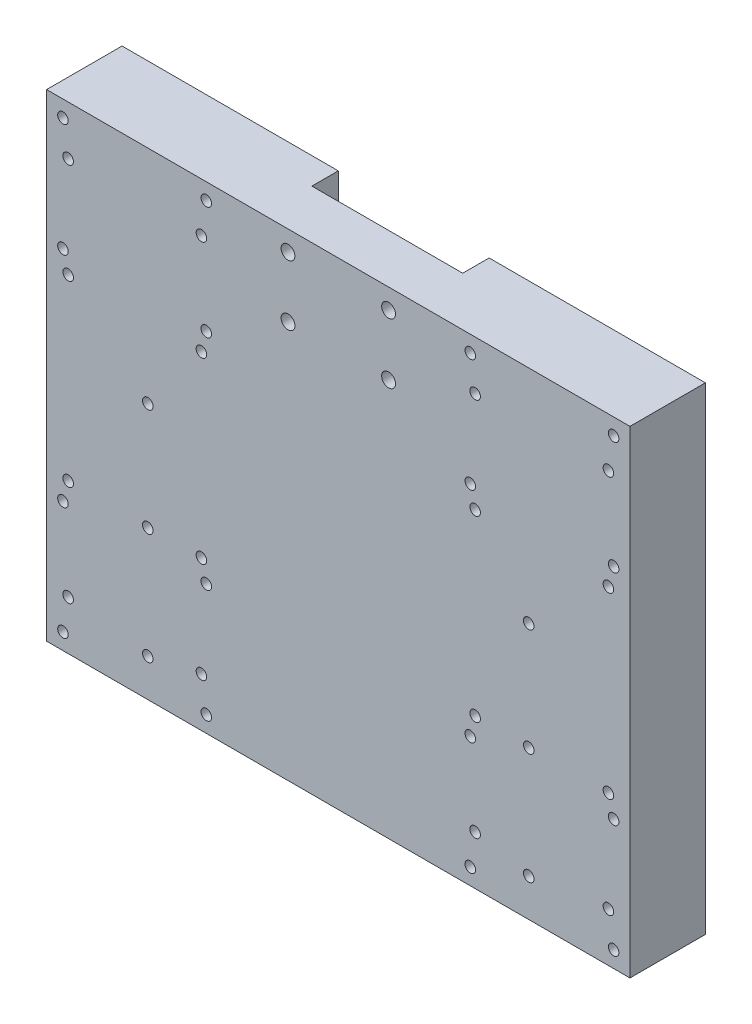
SolidWorks part; units mm, degrees
ref_plane "Piano frontale" through (0, 0, 0) normal (0, 0, 1) x (1, 0, 0)
ref_plane "Piano superiore" through (0, 0, 0) normal (0, 1, 0) x (1, 0, 0)
ref_plane "Piano destro" through (0, 0, 0) normal (1, 0, 0) x (0, 0, -1)
sketch "Schizzo1" plane through (0, 0, 0) normal (0, 0, 1) x (1, 0, 0)
  line L1 (116, -95) -> (-116, -95)
  line L2 (116, -95) -> (116, 95)
  line L3 (116, 95) -> (-116, 95)
  line L4 (-116, -95) -> (-116, 95)
  line L5 (116, -95) -> (-116, 95) construction
  line L6 (116, 95) -> (-116, -95) construction
  point P0 (0, 0)
  dimension "D1" = 232
  dimension "D2" = 190
extrude "Estrusione-Estrusione1" add sketch "Schizzo1" along normal blind 30
sketch "Schizzo3" plane through (0, 0, 30) normal (0, 0, 1) x (1, 0, 0)
  line L0 (20, 7) -> (-20, 7) construction
  line L1 (-20, 7) -> (20, -17) construction
  line L2 (20, -17) -> (20, 7) construction
  line L3 (20, 7) -> (-20, -17) construction
  line L4 (-20, -17) -> (-20, 7) construction
  line L5 (-20, -17) -> (20, -17) construction
  circle A8 centre (20, 7) radius 3
  circle A9 centre (-20, 7) radius 3
  circle A10 centre (-20, -17) radius 3
  circle A11 centre (20, -17) radius 3
  point P21 (0, -5)
  dimension "D1" = 40
  dimension "D2" = 24
sketch "Schizzo4" plane through (0, 95, 0) normal (0, 1, 0) x (1, 0, 0)
  line L0 (116, 0) -> (-116, 0) construction
  line L1 (30, 0) -> (-30, 0)
  line L2 (30, 0) -> (30, -10.5)
  line L3 (30, -10.5) -> (-30, -10.5)
  line L4 (-30, 0) -> (-30, -10.5)
  dimension "D1" = 10.5
extrude "Taglio-Estrusione2" cut sketch "Schizzo4" against normal through all
sketch "Sketch1" plane through (0, 0, 0) normal (0, 0, -1) x (-1, 0, 0)
  line L0 (-52.5, 88.5) -> (-109.5, 88.5) construction
  line L1 (-81, 88.5) -> (-80, -95) construction
  point P0 (-109.5, 88.5)
  point P1 (-109.5, 43.5)
  point P3 (-52.5, 88.5)
  point P5 (-52.5, 43.5)
  point P7 (-52.5, -43.5)
  point P9 (-109.5, -43.5)
  point P11 (-109.5, -88.5)
  point P13 (-52.5, -88.5)
  point P15 (52.5, -88.5)
  point P17 (109.5, -88.5)
  point P19 (109.5, -43.5)
  point P21 (52.5, -43.5)
  point P23 (52.5, 43.5)
  point P25 (109.5, 43.5)
  point P27 (109.5, 88.5)
  point P29 (52.5, 88.5)
hole_wizard "Tap Drill for M5 Tap1" positions "Sketch2" profile "Sketch3" hole size "M5" standard "ISO" end condition through all
sketch "Sketch2" plane through (0, 0, 0) normal (0, 0, -1) x (-1, 0, 0)
  line L0 (-52.5, 88.5) -> (52.5, 88.5) construction
  line L3 (0, 95) -> (0, -95) construction
  line L4 (-116, 95) -> (116, 95) construction
  line L5 (116, -95) -> (-116, -95) construction
  line L7 (116, 0) -> (-116, 0) construction
  line L8 (116, 95) -> (116, -95) construction
  line L9 (-116, -95) -> (-116, 95) construction
  line L13 (-54.4288, 75.5) -> (-107.4288, 75.5)
  line L14 (-54.4288, 75.5) -> (-54.4288, 35.5)
  line L15 (-54.4288, 35.5) -> (-107.4288, 35.5)
  line L16 (-107.4288, 75.5) -> (-107.4288, 35.5)
  circle A1 centre (-52.5, 88.5) radius 2.5
  point P0 (-109.5, 88.5)
  point P3 (-109.5, 43.5)
  point P6 (-52.5, 43.5)
  point P9 (-52.5, 88.5)
  point P12 (52.5, 88.5)
  point P15 (109.5, 88.5)
  point P18 (109.5, 43.5)
  point P21 (52.5, 43.5)
  point P24 (52.5, -43.5)
  point P27 (109.5, -43.5)
  point P30 (109.5, -88.5)
  point P33 (52.5, -88.5)
  point P36 (-52.5, -88.5)
  point P39 (-52.5, -43.5)
  point P42 (-109.5, -43.5)
  point P45 (-109.5, -88.5)
  point P72 (-54.4288, 75.5)
  point P76 (-107.4288, 35.5)
  point P681 (-107.4288, -75.5)
  point P682 (-107.4288, -35.5)
  point P683 (-54.4288, -35.5)
  point P684 (-54.4288, -75.5)
  point P685 (54.4288, -75.5)
  point P686 (54.4288, -35.5)
  point P687 (107.4288, -35.5)
  point P688 (107.4288, -75.5)
  point P689 (107.4288, 75.5)
  point P690 (107.4288, 35.5)
  point P691 (54.4288, 35.5)
  point P692 (54.4288, 75.5)
  point P695 (-107.4288, 75.5)
  point P699 (-54.4288, 35.5)
  dimension "D4" = 5
  dimension "D1" = 53
  dimension "D2" = 40
sketch "Sketch3" plane through (109.5, 88.5, 0) normal (1, 0, 0) x (0, 1, 0)
  line L0 (0, 0) -> (0, 30)
  line L1 (0, 30) -> (2.1, 30)
  line L2 (2.1, 30) -> (2.1, 0)
  line L5 (2.1, 0) -> (0, 0)
  line L11 (0, -6.35) -> (0, 107.95) construction
  dimension "Thru Hole Dia." = 4.2
  dimension "Thru Hole Depth" = 30
hole_wizard "M5 Clearance Hole1" positions "Sketch4" profile "Sketch5" hole size "M5" standard "ISO" end condition through all
sketch "Sketch4" plane through (0, 0, 30) normal (0, 0, 1) x (1, 0, 0)
  point P0 (-20, 87)
  point P3 (20, 87)
  point P6 (20, 63)
  point P9 (-20, 63)
sketch "Sketch5" plane through (-20, 87, 30) normal (1, 0, 0) x (0, -1, 0)
  line L0 (0, 0) -> (0, 30)
  line L1 (0, 30) -> (2.75, 30)
  line L2 (2.75, 30) -> (2.75, 0)
  line L5 (2.75, 0) -> (0, 0)
  line L11 (0, -6.35) -> (0, 107.95) construction
  dimension "Thru Hole Dia." = 5.5
  dimension "Thru Hole Depth" = 30
hole_wizard "Tap Drill for M5 Tap3" positions "Sketch6" profile "Sketch7" hole size "M5" standard "ISO" end condition up to next
sketch "Sketch6" plane through (0, 0, 30) normal (0, 0, 1) x (1, 0, 0)
  point P0 (-75.75, 7)
  point P6 (-75.75, -80)
  point P8 (75.75, 7)
  point P14 (75.75, -80)
  point P23 (-75.75, -35.7925)
  point P25 (75.75, -35.7925)
sketch "Sketch7" plane through (-75.75, 7, 30) normal (1, 0, 0) x (0, -1, 0)
  line L0 (0, 0) -> (0, 30)
  line L1 (0, 30) -> (2.1, 30)
  line L2 (2.1, 30) -> (2.1, 0)
  line L5 (2.1, 0) -> (0, 0)
  line L11 (0, -6.35) -> (0, 107.95) construction
  dimension "Thru Hole Dia." = 4.2
  dimension "Thru Hole Depth" = 30
